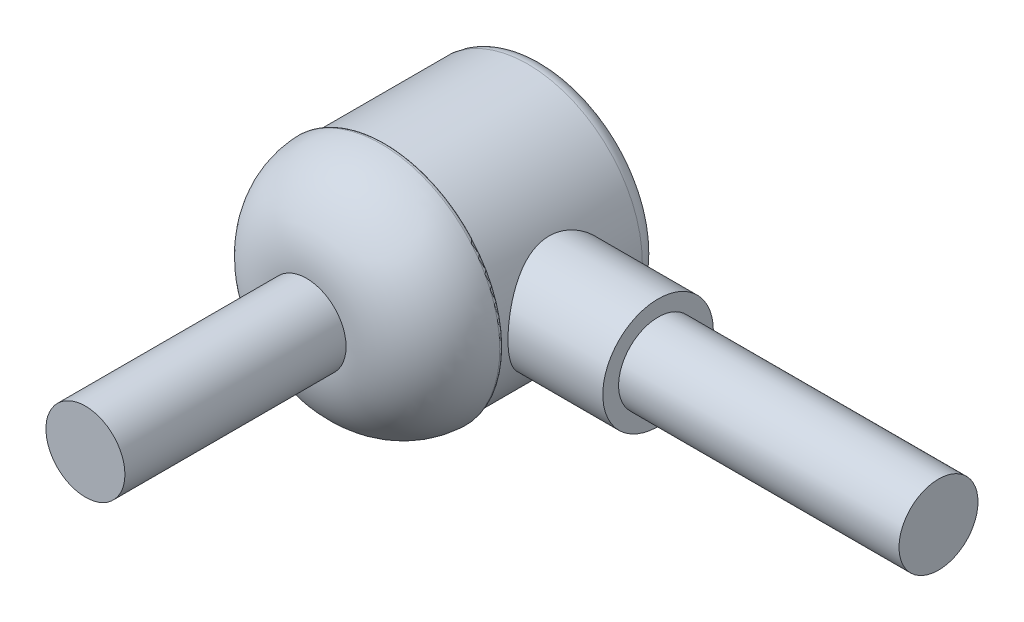
SolidWorks part; units mm, degrees
ref_plane "Płaszczyzna przednia" through (0, 0, 0) normal (0, 0, 1) x (1, 0, 0)
ref_plane "Płaszczyzna górna" through (0, 0, 0) normal (0, 1, 0) x (1, 0, 0)
ref_plane "Płaszczyzna prawa" through (0, 0, 0) normal (1, 0, 0) x (0, 0, -1)
sketch "Szkic1" plane through (0, 0, 0) normal (0, 0, 1) x (1, 0, 0)
  circle A0 centre (0, 0) radius 14.5
  dimension "D1" = 29
extrude "Dodanie-wyciągnięcie1" add sketch "Szkic1" along normal blind 20
sketch "Szkic2" plane through (0, 0, 20) normal (0, 0, 1) x (1, 0, 0)
  circle A0 centre (0, 0) radius 15
  dimension "D1" = 30
extrude "Dodanie-wyciągnięcie2" add sketch "Szkic2" along normal blind 10
fillet "Zaokrąglenie1" radius 10 1 edges at (15, 0, 30)
sketch "Szkic3" plane through (0, 0, 30) normal (0, 0, 1) x (1, 0, 0)
  circle A0 centre (0, 0) radius 5
  dimension "D1" = 10
extrude "Dodanie-wyciągnięcie3" add sketch "Szkic3" along normal blind 28
fillet "Zaokrąglenie2" radius 0.5 1 edges at (15, 0, 20)
fillet "Zaokrąglenie3" radius 2 1 edges at (14.5, 0, 0)
ref_plane "Płaszczyzna1" through (26.5, 0, 0) normal (1, 0, 0) x (0, 0, -1)
sketch "Szkic4" plane through (26.5, 0, 0) normal (1, 0, 0) x (0, 0, -1)
  line L0 (16.4855, 0) -> (-16.4855, 0) construction
  line L1 (-20, 14.5) -> (-20, -14.5) construction
  circle A0 centre (-12, 0) radius 7
  dimension "D1" = 14
  dimension "D2" = 8
extrude "Dodanie-wyciągnięcie4" add sketch "Szkic4" against normal up to next
sketch "Szkic5" plane through (26.5, 0, 0) normal (1, 0, 0) x (0, 0, -1)
  circle A0 centre (-12, 0) radius 5
  dimension "D1" = 10
extrude "Dodanie-wyciągnięcie5" add sketch "Szkic5" along normal blind 35.5
